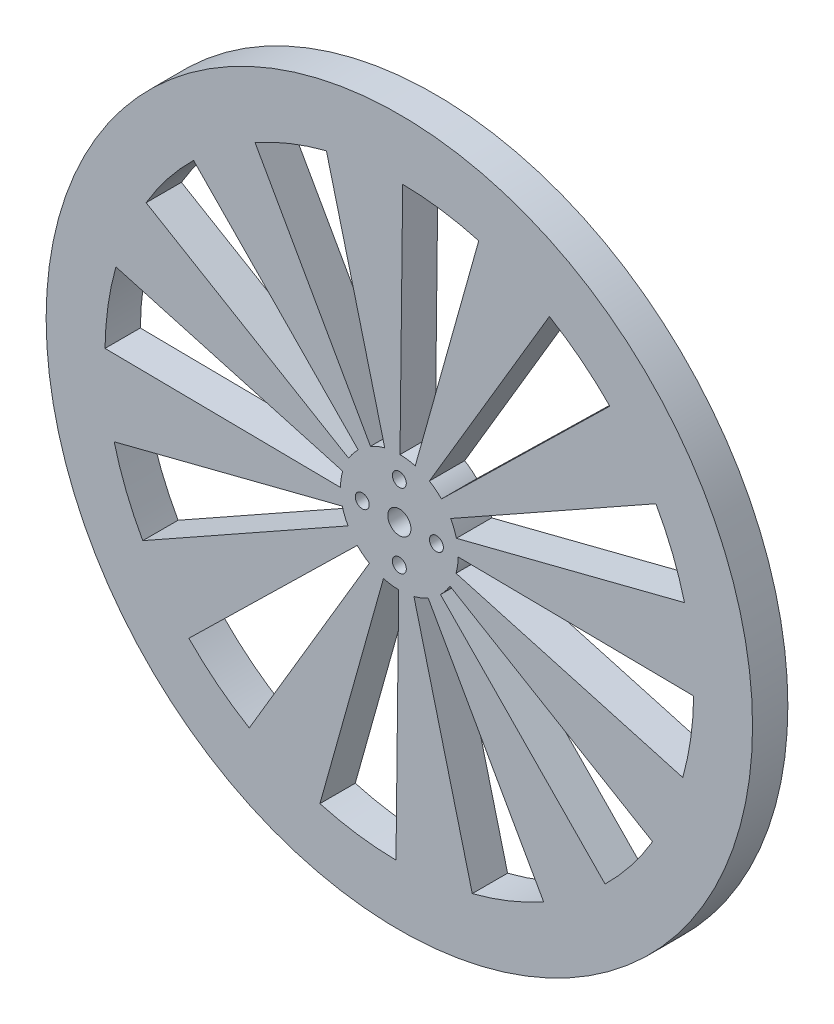
SolidWorks part; units mm, degrees
ref_plane "Front Plane" through (0, 0, 0) normal (0, 0, 1) x (1, 0, 0)
ref_plane "Top Plane" through (0, 0, 0) normal (0, 1, 0) x (1, 0, 0)
ref_plane "Right Plane" through (0, 0, 0) normal (1, 0, 0) x (0, 0, -1)
sketch "Sketch2" plane through (0, 0, 0) normal (0, 0, 1) x (1, 0, 0)
  circle A0 centre (0, 0) radius 76.2
  dimension "D1" = 152.4
extrude "Boss-Extrude1" add sketch "Sketch2" along normal blind 7.62
sketch "Sketch5" plane through (0, 0, 7.62) normal (0, 0, 1) x (1, 0, 0)
  line L0 (0, 0) -> (32.3742, 54.6275)
  line L1 (0, 0) -> (45.4097, 44.3871)
  line L2 (0, 0) -> (61.5195, 15.7355)
  line L3 (0, 0) -> (55.3506, 31.1217)
  line L4 (0, 0) -> (61.1452, -17.1324)
  line L5 (0, 0) -> (63.4959, -0.7231)
  line L6 (0, 0) -> (44.3871, -45.4097)
  line L7 (0, 0) -> (54.6275, -32.3742)
  line L8 (0, 0) -> (15.7355, -61.5195)
  line L9 (0, 0) -> (31.1217, -55.3506)
  line L10 (0, 0) -> (-17.1324, -61.1452)
  line L11 (0, 0) -> (-0.7231, -63.4959)
  line L12 (0, 0) -> (-45.4097, -44.3871)
  line L13 (0, 0) -> (-32.3742, -54.6275)
  line L14 (0, 0) -> (-61.5195, -15.7355)
  line L15 (0, 0) -> (-55.3506, -31.1217)
  line L16 (0, 0) -> (-61.1452, 17.1324)
  line L17 (0, 0) -> (-63.4959, 0.7231)
  line L18 (0, 0) -> (-44.3871, 45.4097)
  line L19 (0, 0) -> (-54.6275, 32.3742)
  line L20 (0, 0) -> (-15.7355, 61.5195)
  line L21 (0, 0) -> (-31.1217, 55.3506)
  line L22 (0, 0) -> (17.1324, 61.1452)
  line L23 (0, 0) -> (0.7231, 63.4959)
  circle A0 centre (0, 0) radius 12.7
  circle A1 centre (0, 0) radius 63.5
  point P30 (0, 0)
  dimension "D1" = 25.4
  dimension "D2" = 127
  dimension "D3" = 15
  dimension "D4" = 44.3871
  dimension "D5" = 12
extrude "Cut-Extrude3" cut sketch "Sketch5" against normal through all contours L22 A1 L23 A0 | L1 A1 L0 A0 | L2 A1 L3 A0 | L4 A1 L5 A0 | L6 A1 L7 A0 | L8 A1 L9 A0 | L10 A1 L11 A0 | L12 A1 L13 A0 | L14 A1 L15 A0 | L16 A1 L17 A0 | L18 A1 L19 A0 | L20 A1 L21 A0 region at (26.9463, 34.3012, 7.62) region at (40.4868, 16.2325, 7.62) region at (43.1788, -6.1856, 7.62) region at (34.3012, -26.9463, 7.62) region at (16.2325, -40.4868, 7.62) region at (-6.1856, -43.1788, 7.62) region at (-26.9463, -34.3012, 7.62) region at (-40.4868, -16.2325, 7.62) region at (-43.1788, 6.1856, 7.62) region at (-34.3012, 26.9463, 7.62) region at (-16.2325, 40.4868, 7.62) region at (6.1856, 43.1788, 7.62)
sketch "Sketch6" plane through (0, 0, 7.62) normal (0, 0, 1) x (1, 0, 0)
  circle A3 centre (0, 8) radius 1.5
  arc A4 (3.4265, 12.229) -> (0.1446, 12.6992) centre (0, 0) ccw construction
  point P6 (1.801, 12.5717)
  dimension "D1" = 3
  dimension "D2" = 8
  dimension "D3" = 4.5717
extrude "Cut-Extrude4" cut sketch "Sketch6" against normal through all contours A3
pattern_circular "CirPattern1" count 4 over 360 about axis through (0, 0, 7.62) along (0, 0, 1) of "Cut-Extrude4"
sketch "Sketch7" plane through (0, 0, 7.62) normal (0, 0, 1) x (1, 0, 0)
  circle A0 centre (0, 0) radius 2.5
  dimension "D1" = 5
extrude "Cut-Extrude5" cut sketch "Sketch7" against normal through all
